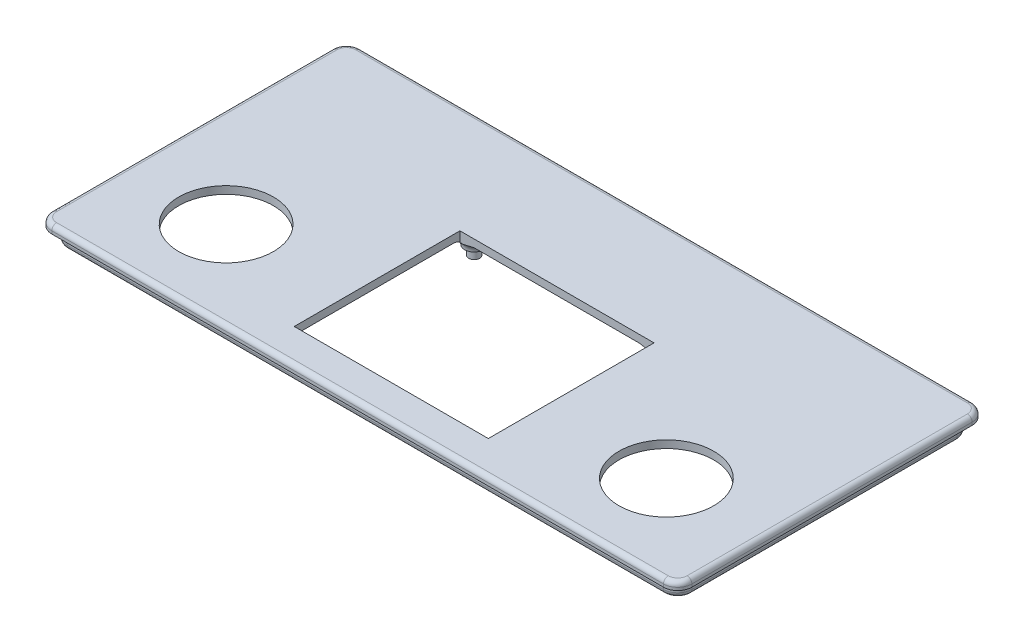
SolidWorks part; units mm, degrees
ref_plane "Спереди" through (0, 0, 0) normal (0, 0, 1) x (1, 0, 0)
ref_plane "Сверху" through (0, 0, 0) normal (0, 1, 0) x (1, 0, 0)
ref_plane "Справа" through (0, 0, 0) normal (1, 0, 0) x (0, 0, -1)
sketch "Sketch1" plane through (0, 0, 0) normal (0, 1, 0) x (1, 0, 0)
  line L0 (-64.4, -29.4) -> (-64.4, 29.4)
  line L1 (-66, -31) -> (66, -31)
  line L2 (-66, -31) -> (-66, 31)
  line L3 (-66, 31) -> (66, 31)
  line L4 (66, -31) -> (66, 31)
  line L5 (-66, -31) -> (66, 31) construction
  line L6 (-66, 31) -> (66, -31) construction
  line L7 (-64.4, 29.4) -> (64.4, 29.4)
  line L8 (64.4, -29.4) -> (64.4, 29.4)
  line L9 (-64.4, -29.4) -> (64.4, -29.4)
  point P0 (0, 0)
  dimension "D1" = 132
  dimension "D2" = 62
  dimension "D3" = 1.6
extrude "Boss-Extrude1" add sketch "Sketch1" along normal blind 3
sketch "Sketch3" plane through (0, 3, 0) normal (0, 1, 0) x (1, 0, 0)
  line L24 (67.6, -32.6) -> (67.6, 32.6)
  line L25 (-67.6, -32.6) -> (67.6, -32.6)
  line L26 (-67.6, 32.6) -> (-67.6, -32.6)
  line L27 (67.6, 32.6) -> (-67.6, 32.6)
  line L28 (67.6, -32.6) -> (67.6, 32.6)
  line L29 (-67.6, -32.6) -> (67.6, -32.6)
  line L30 (-67.6, 32.6) -> (-67.6, -32.6)
  line L31 (67.6, 32.6) -> (-67.6, 32.6)
  dimension "D1" = 1.6
extrude "Boss-Extrude3" add sketch "Sketch3" along normal blind 1.6
fillet "Fillet2" radius 3 12 edges at (-64.4, 1.5, 29.4) (-64.4, 1.5, -29.4) (64.4, 1.5, -29.4) (64.4, 1.5, 29.4) (66, 1.5, -31) (67.6, 3.8, -32.6) (67.6, 3.8, 32.6) (66, 1.5, 31) (-66, 1.5, -31) (-67.6, 3.8, -32.6) (-67.6, 3.8, 32.6) (-66, 1.5, 31)
sketch "Sketch4" plane through (0, 4.6, 0) normal (0, 1, 0) x (1, 0, 0)
  circle A0 centre (-46.3929, -14) radius 10
  circle A1 centre (46.6071, -14) radius 10
  dimension "D1" = 20
extrude "Cut-Extrude1" cut sketch "Sketch4" against normal up to next
fillet "Fillet3" radius 1 8 edges at (66.7213, 4.6, -31.7213) (67.6, 4.6, 0) (66.7213, 4.6, 31.7213) (0, 4.6, 32.6) (-66.7213, 4.6, 31.7213) (-67.6, 4.6, 0) (-66.7213, 4.6, -31.7213) (0, 4.6, -32.6)
fillet "Fillet4" radius 1 8 edges at (-65.1213, 0, 30.1213) (-66, 0, 0) (-65.1213, 0, -30.1213) (0, 0, -31) (65.1213, 0, -30.1213) (66, 0, 0) (65.1213, 0, 30.1213) (0, 0, 31)
sketch "Sketch5" plane through (0, 4.6, 0) normal (0, 1, 0) x (1, 0, 0)
  line L1 (-20.5, -25.5) -> (20.5, -25.5)
  line L2 (-20.5, -25.5) -> (-20.5, 9.5)
  line L3 (-20.5, 9.5) -> (20.5, 9.5)
  line L4 (20.5, -25.5) -> (20.5, 9.5)
  line L5 (-20.5, -25.5) -> (20.5, 9.5) construction
  line L6 (-20.5, 9.5) -> (20.5, -25.5) construction
  circle A0 centre (-46.3929, -14) radius 10 construction
  point P0 (0, -8)
  point P7 (0, 0)
  point P8 (0, 0)
  dimension "D3" = 6
  dimension "D1" = 35
  dimension "D2" = 41
extrude "Cut-Extrude2" cut sketch "Sketch5" against normal up to next
sketch "Sketch6" plane through (0, 3, 0) normal (0, -1, 0) x (1, 0, 0)
  circle A0 centre (-20.125, -12.1338) radius 2
  circle A1 centre (-20.125, 27.6395) radius 2
  circle A2 centre (20.125, 27.6395) radius 2
  circle A3 centre (20.125, -12.1338) radius 2
  dimension "D1" = 4
extrude "Boss-Extrude4" add sketch "Sketch6" along normal blind 2
sketch "Sketch7" plane through (0, 1, 0) normal (0, -1, 0) x (1, 0, 0)
  circle A0 centre (-20.125, 27.6395) radius 1.15
  circle A1 centre (20.125, 27.6395) radius 1.15
  circle A2 centre (-20.125, -12.1338) radius 1.15
  circle A3 centre (20.125, -12.1338) radius 1.15
extrude "Boss-Extrude5" add sketch "Sketch7" along normal blind 2
fillet "Fillet5" radius 2 4 edges at (20.125, 3, 25.6395) (-20.125, 3, 25.6395) (-20.125, 3, -10.1338) (20.125, 3, -10.1338)
